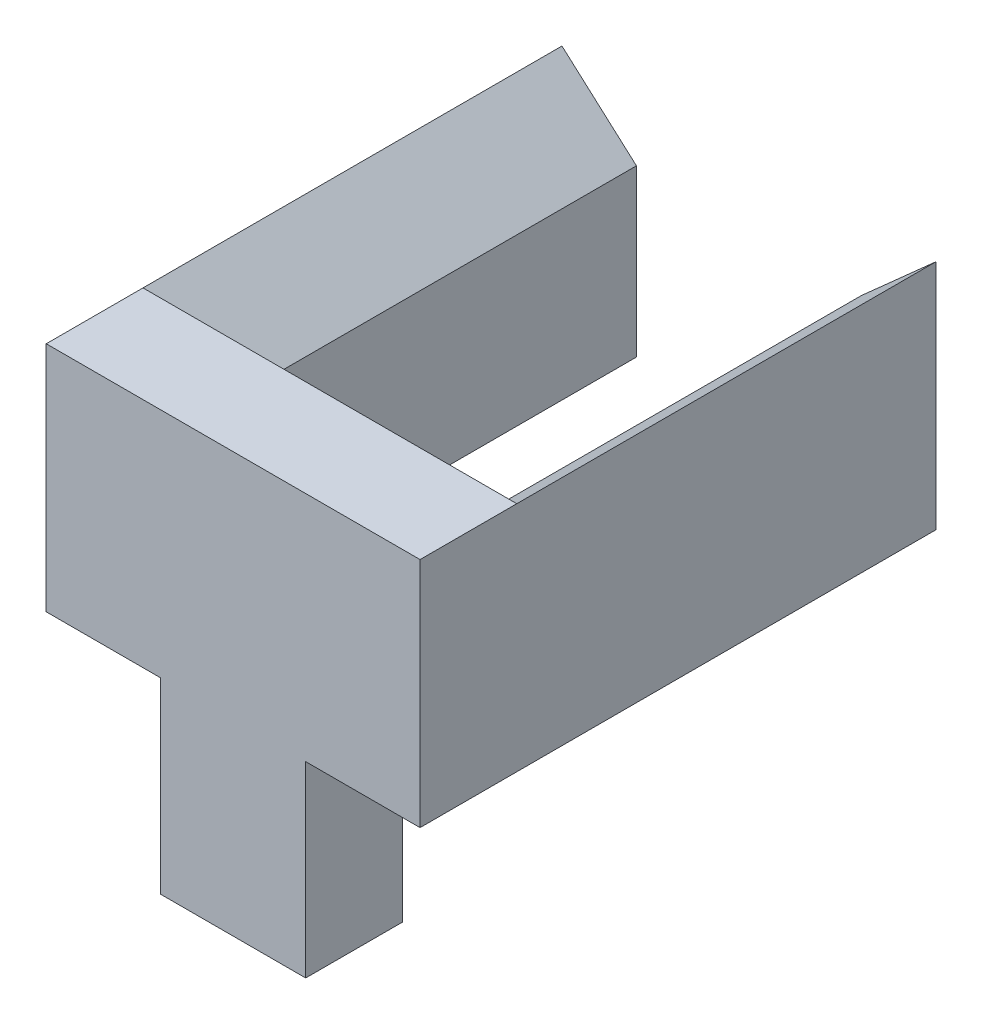
SolidWorks part; units mm, degrees
ref_plane "Front Plane" through (0, 0, 0) normal (0, 0, 1) x (1, 0, 0)
ref_plane "Top Plane" through (0, 0, 0) normal (0, 1, 0) x (1, 0, 0)
ref_plane "Right Plane" through (0, 0, 0) normal (1, 0, 0) x (0, 0, -1)
sketch "Sketch1" plane through (0, 0, 0) normal (0, 1, 0) x (1, 0, 0)
  line L0 (-13.9881, 12.8425) -> (-13.9881, -12.5575)
  line L1 (-13.9881, -12.5575) -> (24.1119, -12.5575)
  line L2 (24.1119, -12.5575) -> (24.1119, 12.8425)
  line L3 (24.1119, 12.8425) -> (-13.9881, 12.8425)
  line L4 (5.0619, 12.8425) -> (5.0619, -12.5575) construction
extrude "Boss-Extrude1" add sketch "Sketch1" along normal blind 110.1598 contours L3 L0 L1 L2
sketch "Sketch2" plane through (24.1119, 0, 0) normal (1, 0, 0) x (0, 0, -1)
  line L0 (-12.5575, 110.1598) -> (12.8425, 110.1598)
  line L1 (12.8425, 110.1598) -> (12.8425, 49.1998)
  line L2 (12.8425, 110.1598) -> (12.8425, 0) construction
  line L3 (12.8425, 49.1998) -> (-12.5575, 49.1998)
  line L4 (-12.5575, 110.1598) -> (-12.5575, 0) construction
  line L5 (-12.5575, 49.1998) -> (-12.5575, 110.1598)
extrude "Boss-Extrude2" add sketch "Sketch2" along normal blind 30.0228 contours L1 L3 L5 L0
sketch "Sketch3" plane through (-13.9881, 0, 0) normal (-1, 0, 0) x (0, 0, 1)
  line L0 (12.5575, 110.1598) -> (12.5575, 0) construction
  line L1 (-12.8425, 110.1598) -> (12.5575, 110.1598)
  line L2 (-12.8425, 110.1598) -> (-12.8425, 49.1998)
  line L3 (-12.8425, 49.1998) -> (12.5575, 49.1998)
  line L4 (12.5575, 110.1598) -> (12.5575, 49.1998)
extrude "Boss-Extrude3" add sketch "Sketch3" along normal blind 30.0228
sketch "Sketch4" plane through (0, 0, -12.8425) normal (0, 0, -1) x (-1, 0, 0)
  line L0 (-54.1347, 110.1598) -> (-54.1347, 49.1998)
  line L4 (-34.5767, 92.6998) -> (-54.1347, 110.1598)
  line L5 (-34.5767, 92.6998) -> (-34.5767, 49.1998)
  line L6 (-54.1347, 49.1998) -> (-24.1119, 49.1998) construction
  line L7 (-34.5767, 49.1998) -> (-54.1347, 49.1998)
extrude "Boss-Extrude4" add sketch "Sketch4" along normal blind 110.0074
sketch "Sketch5" plane through (0, 0, -12.8425) normal (0, 0, -1) x (-1, 0, 0)
  line L0 (44.0109, 110.1598) -> (44.0109, 49.1998)
  line L1 (44.0109, 49.1998) -> (24.4529, 49.1998)
  line L2 (44.0109, 49.1998) -> (13.9881, 49.1998) construction
  line L3 (24.4529, 49.1998) -> (24.4529, 92.6998)
  line L4 (24.4529, 92.6998) -> (44.0109, 110.1598)
extrude "Boss-Extrude5" add sketch "Sketch5" along normal blind 110.0074 contours L4 L0 L1 L3
sketch "Sketch8" plane through (0, 0, 0) normal (0, -1, 0) x (1, 0, 0)
  line L0 (5.0619, 12.5575) -> (5.0619, -12.8425) construction
  line L1 (-13.9881, 12.5575) -> (24.1119, 12.5575) construction
  line L2 (24.1119, -12.8425) -> (-13.9881, -12.8425) construction
  line L3 (5.0619, -0.1425) -> (15.0619, -0.1425) construction
  line L4 (5.0619, -0.1425) -> (-4.9381, -0.1425) construction
  circle A0 centre (-4.9381, -0.1425) radius 3.81
  circle A1 centre (15.0619, -0.1425) radius 3.81
  dimension "D1" = 7.62
  dimension "D2" = 7.62
extrude "Cut-Extrude1" cut sketch "Sketch8" against normal blind 25.4
